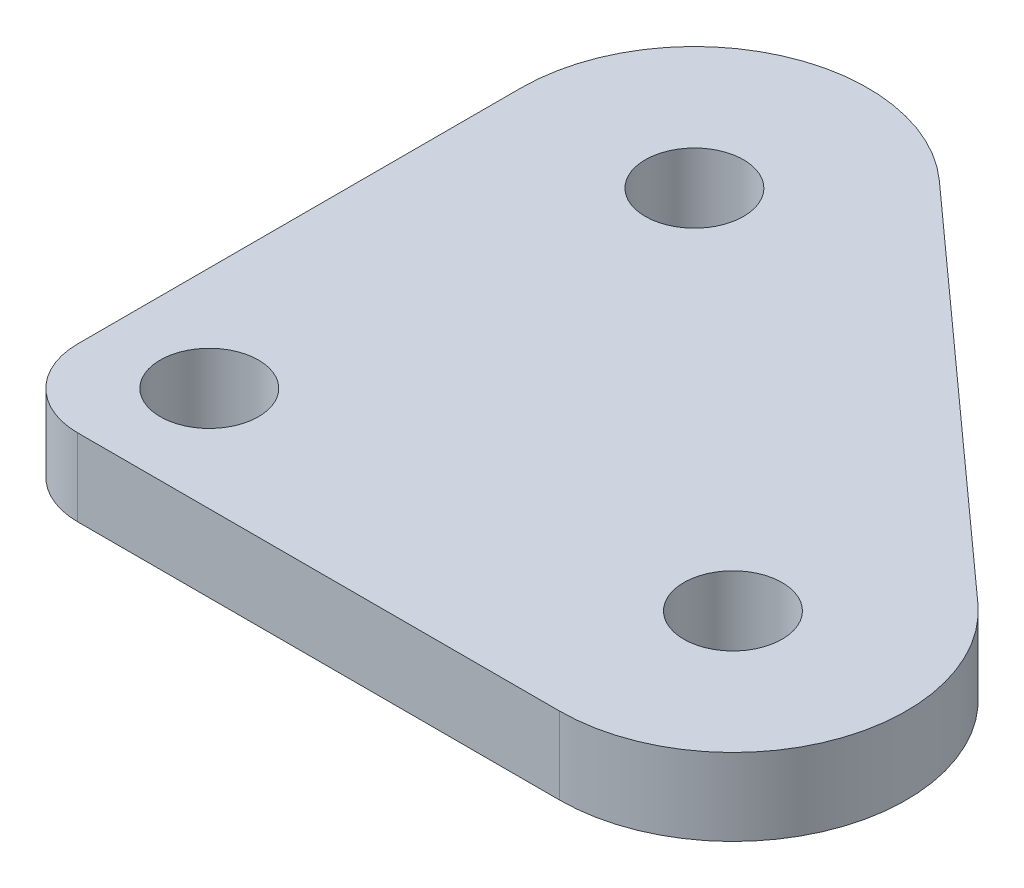
SolidWorks part; units mm, degrees
ref_plane "Front Plane" through (0, 0, 0) normal (0, 0, 1) x (1, 0, 0)
ref_plane "Top Plane" through (0, 0, 0) normal (0, 1, 0) x (1, 0, 0)
ref_plane "Right Plane" through (0, 0, 0) normal (1, 0, 0) x (0, 0, -1)
sketch "Sketch1" plane through (0, 0, 0) normal (0, 1, 0) x (1, 0, 0)
  line L0 (0, 0) -> (20, 0)
  line L1 (20, 0) -> (20, 18)
  line L2 (0, 0) -> (0, 18)
  line L3 (20, -9) -> (-9, -9)
  line L4 (-9, -9) -> (-9, 18)
  line L5 (6.0207, 24.6896) -> (26.0207, 6.6896)
  circle A0 centre (0, 18) radius 9
  circle A1 centre (20, 0) radius 9
  circle A2 centre (0, 18) radius 2.55
  circle A3 centre (20, 0) radius 2.55
  dimension "D4" = 18
  dimension "D5" = 18
  dimension "D6" = 5.1
  dimension "D7" = 5.1
  dimension "D1" = 20
  dimension "D2" = 18
  dimension "D3" = 18
extrude "Boss-Extrude1" add sketch "Sketch1" along normal blind 4 contours A1 L0 L2 A0 L4 L3 | A1 L1 L5 A0 L2 L0 | A1 L5 L1 | A2 A0 | A3 L0 A1 L1 | A3 L1 A1 L0 region at (9.3325, 0, -8.9277) region at (-0.27, 0, 1.27) region at (15.9413, 0, -4.0587) region at (14.225, 0, 0.2546) region at (-6.184, 0, -11.816) region at (21.5909, 0, -9.7233)
fillet "Fillet1" radius 4 1 edges at (-9, 2, 9)
sketch "Sketch2" plane through (0, 0, 0) normal (0, -1, 0) x (1, 0, 0)
  line L2 (-3.5858, 9) -> (-3.5858, 3.5858)
  line L3 (20, 9) -> (-5, 9) construction
  line L4 (-3.5858, 3.5858) -> (-9, 3.5858)
  line L5 (-9, 5) -> (-9, -18) construction
  circle A0 centre (-3.5858, 3.5858) radius 2.55
  arc A1 (-5, 9) -> (-9, 5) centre (-5, 5) ccw construction
  dimension "D1" = 5.1
  dimension "D2" = 2
extrude "Cut-Extrude1" cut sketch "Sketch2" against normal blind 4 contours L4 A0 L2 | L2 A0 L4 region at (-3.225, 0, 3.225) region at (-4.668, 0, 4.668)
sketch "Sketch3" plane through (0, 4, 0) normal (0, 1, 0) x (1, 0, 0)
  line L0 (-3.5858, -3.5858) -> (20, 0)
  line L1 (20, 0) -> (-3.5858, 0)
  line L2 (-3.5858, 0) -> (-3.5858, -3.5858)
  line L3 (20, 0) -> (0, 18)
  line L4 (0, 18) -> (0, 0)
  line L5 (0, 0) -> (20, 0)
